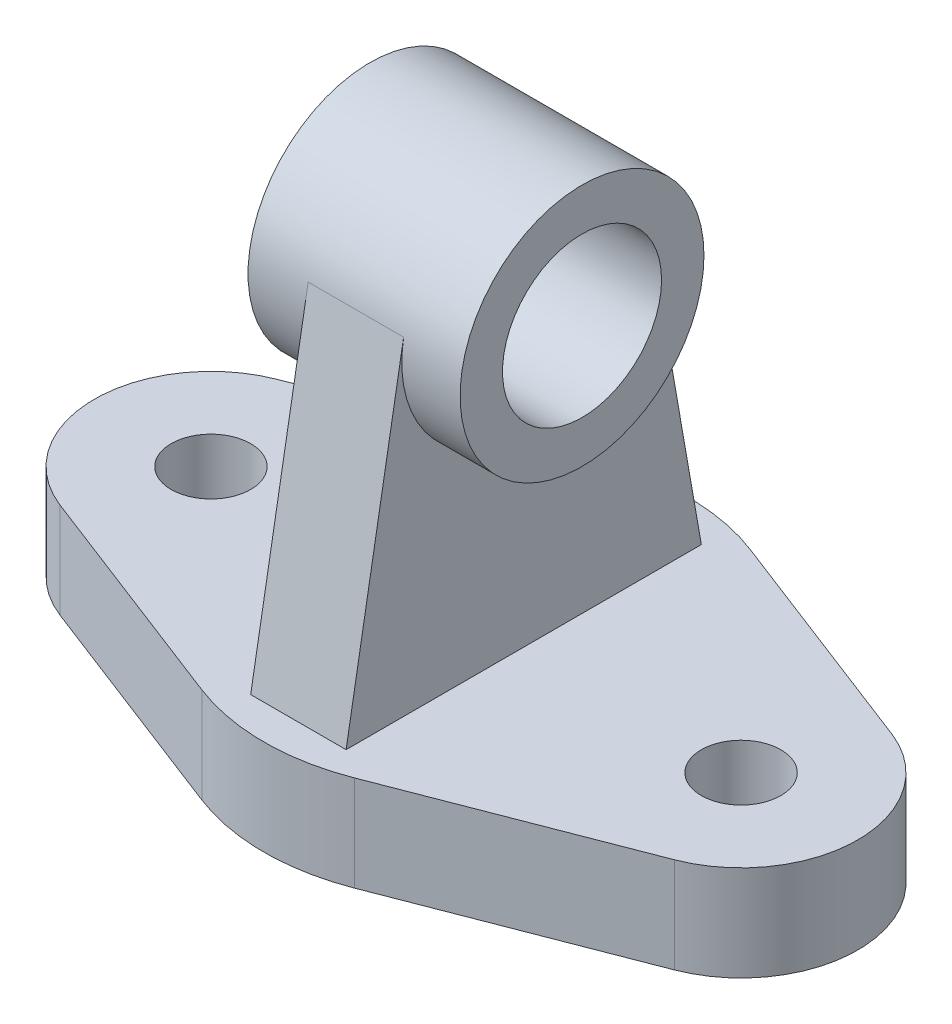
SolidWorks part; units mm, degrees
ref_plane "前基準面" through (0, 0, 0) normal (0, 0, 1) x (1, 0, 0)
ref_plane "上基準面" through (0, 0, 0) normal (0, 1, 0) x (1, 0, 0)
ref_plane "右基準面" through (0, 0, 0) normal (1, 0, 0) x (0, 0, -1)
sketch "草圖1" plane through (0, 0, 0) normal (0, 1, 0) x (1, 0, 0)
  line L0 (-107.7551, 0) -> (118.9796, 0) construction
  line L1 (0, 68.3673) -> (0, -42.8746) construction
  line L2 (-57.92, -20.525) -> (-14.4, -37.3181)
  line L3 (14.4, -37.3181) -> (57.92, -20.525)
  line L4 (57.92, 20.525) -> (14.4, 37.3181)
  line L5 (-14.4, 37.3181) -> (-57.92, 20.525)
  circle A0 centre (50, 0) radius 7.5
  circle A1 centre (-50, 0) radius 7.5
  arc A2 (-57.92, -20.525) -> (-57.92, 20.525) centre (-50, 0) cw
  arc A3 (57.92, -20.525) -> (57.92, 20.525) centre (50, 0) ccw
  arc A4 (14.4, -37.3181) -> (-14.4, -37.3181) centre (0, 0) cw
  arc A5 (14.4, 37.3181) -> (-14.4, 37.3181) centre (0, 0) ccw
  point P0 (0, 52.3547)
  point P11 (0, 0)
  point P13 (0, 0)
  point P14 (91.8367, 0)
  point P15 (-90.8163, 0)
  point P18 (-111.1111, 0)
  point P21 (111.1111, 0)
  point P22 (0, 0)
  point P28 (0, 42.8746)
  dimension "D2" = 15
  dimension "D3" = 22
  dimension "D4" = 40
  dimension "D1" = 100
extrude "填料-伸長1" add sketch "草圖1" along normal blind 18
sketch "草圖2" plane through (0, 0, 0) normal (1, 0, 0) x (0, 0, -1)
  line L0 (20.525, 18) -> (-20.525, 18) construction
  line L1 (20.525, 18) -> (-20.525, 18) construction
  line L2 (-22.6557, 79.9649) -> (-33.5, 18)
  line L3 (-37.3181, 18) -> (-20.525, 18) construction
  line L4 (22.6557, 79.9649) -> (33.5, 18)
  line L5 (20.525, 18) -> (37.3181, 18) construction
  line L6 (-33.5, 18) -> (33.5, 18)
  circle A0 centre (0, 76) radius 23
  circle A1 centre (0, 76) radius 15
  dimension "D1" = 46
  dimension "D3" = 30
  dimension "D2" = 67
  dimension "D4" = 58
extrude "填料-伸長2" add sketch "草圖2" along normal mid plane 40 separate body contours A0 A1 region at (0, 98.3495, 0)
extrude "填料-伸長3" add sketch "草圖2<3>" along normal mid plane 18 contours A0 L2 L6 L4 region at (0, 38.2253, 0)
sketch "草圖2<3>" plane through (0, 0, 0) normal (1, 0, 0) x (0, 0, -1) same geometry as "草圖2"
